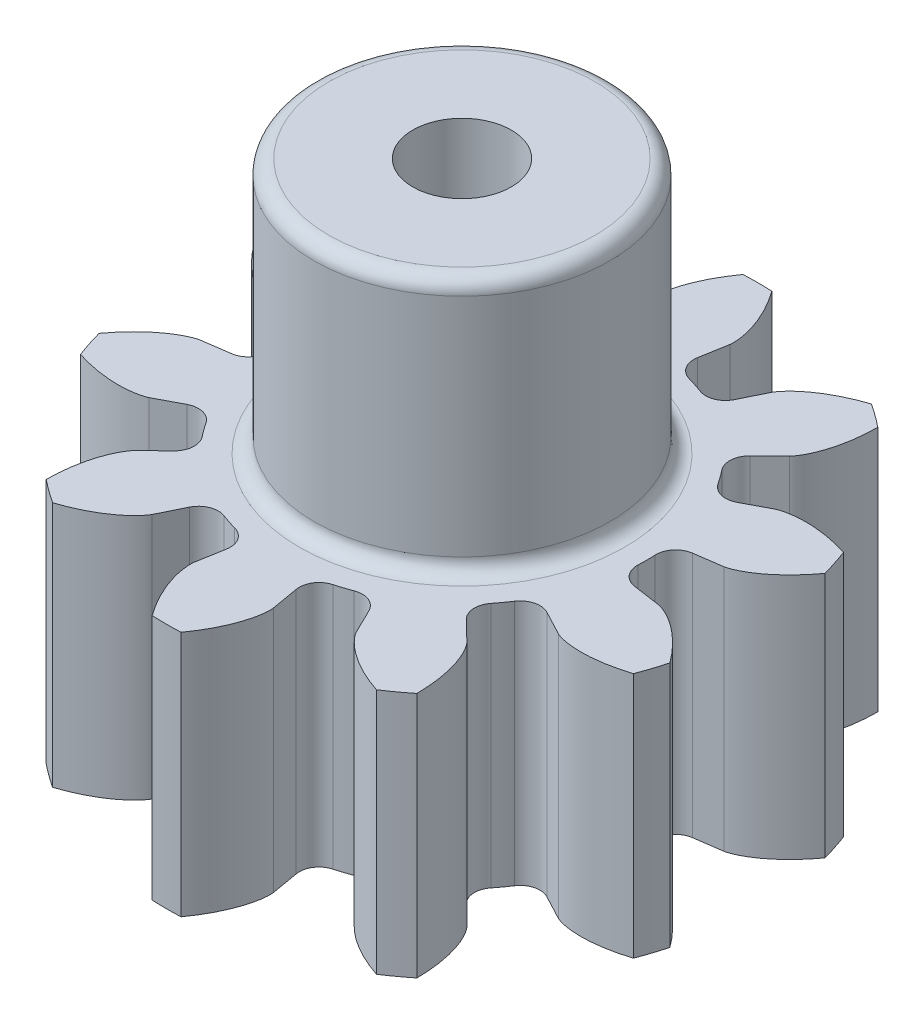
SolidWorks part; units mm, degrees
ref_plane "Front Plane" through (0, 0, 0) normal (0, 0, 1) x (1, 0, 0)
ref_plane "Top Plane" through (0, 0, 0) normal (0, 1, 0) x (1, 0, 0)
ref_plane "Right Plane" through (0, 0, 0) normal (1, 0, 0) x (0, 0, -1)
sketch "Sketch2" plane through (0, 0, 0) normal (0, 1, 0) x (1, 0, 0)
  circle A0 centre (0, 0) radius 15.24
  dimension "D1" = 30.48
extrude "Boss-Extrude1" add sketch "Sketch2" along normal blind 12.7
sketch "Sketch3" plane through (0, 0, 0) normal (0, -1, 0) x (-1, 0, 0)
  line L0 (0, 0) -> (11.8137, -1.691) construction
  line L1 (0, 0) -> (11.8137, 1.691) construction
  line L2 (11.8137, -1.691) -> (9.4289, -1.3497)
  line L3 (11.8137, 1.691) -> (9.4289, 1.3497)
  circle A0 centre (0, 0) radius 15.24
  circle A1 centre (0, 0) radius 12.7
  circle A2 centre (0, 0) radius 11.938
  circle A3 centre (0, 0) radius 9.525
  arc A4 (14.7073, 3.9942) -> (14.7073, -3.9942) centre (0, 0) cw
  arc A5 (9.4289, 1.3497) -> (9.4289, -1.3497) centre (0, 0) cw
  spline S0 degree 4 poles (11.8137, 1.691) (11.8192, 1.6919) (11.8345, 1.6947) (11.8634, 1.701) (11.9102, 1.7129) (11.9692, 1.7305) (12.0448, 1.7558) (12.1329, 1.789) (12.2286, 1.829) (12.3315, 1.8763) (12.433, 1.9267) (12.5329, 1.9801) (12.6314, 2.036) (12.7494, 2.1069) (12.8888, 2.1963) (13.0487, 2.3071) (13.2263, 2.4402) (13.4031, 2.5835) (13.5735, 2.7307) (13.7413, 2.8866) (13.9005, 3.0423) (14.0612, 3.2111) (14.2071, 3.3705) (14.3651, 3.5565) (14.4911, 3.7088) (14.6511, 3.9175) (14.7439, 4.0431) (14.8502, 4.1926) (14.8963, 4.2604) (14.9247, 4.3021) knots 0 0 0 0 0 0.005377 0.015084 0.028532 0.04661 0.064855 0.092111 0.119476 0.146842 0.174209 0.201575 0.228941 0.256307 0.307035 0.361767 0.4165 0.471232 0.525964 0.580697 0.635429 0.690161 0.744894 0.799626 0.854358 0.909091 0.954545 1 1 1 1 1 construction
  spline S1 degree 4 poles (11.8137, 1.691) (11.8192, 1.6919) (11.8345, 1.6947) (11.8634, 1.701) (11.9102, 1.7129) (11.9692, 1.7305) (12.0448, 1.7558) (12.1329, 1.789) (12.2286, 1.829) (12.3315, 1.8763) (12.433, 1.9267) (12.5329, 1.9801) (12.6314, 2.036) (12.7494, 2.1069) (12.8888, 2.1963) (13.0487, 2.3071) (13.2263, 2.4402) (13.4031, 2.5835) (13.5735, 2.7307) (13.7413, 2.8866) (13.9005, 3.0423) (14.0612, 3.2111) (14.2071, 3.3705) (14.3651, 3.5565) (14.4911, 3.7088) (14.6164, 3.8723) (14.6768, 3.9527) (14.7073, 3.9942) knots 0 0 0 0 0 0.005377 0.015084 0.028532 0.04661 0.064855 0.092111 0.119476 0.146842 0.174209 0.201575 0.228941 0.256307 0.307035 0.361767 0.4165 0.471232 0.525964 0.580697 0.635429 0.690161 0.744894 0.799626 0.854358 0.909091 0.909091 0.909091 0.909091 0.909091
  spline S2 degree 4 poles (11.8137, -1.691) (11.8192, -1.6919) (11.8345, -1.6947) (11.8634, -1.701) (11.9102, -1.7129) (11.9692, -1.7305) (12.0448, -1.7558) (12.1329, -1.789) (12.2286, -1.829) (12.3315, -1.8763) (12.433, -1.9267) (12.5329, -1.9801) (12.6314, -2.036) (12.7494, -2.1069) (12.8888, -2.1963) (13.0487, -2.3071) (13.2263, -2.4402) (13.4031, -2.5835) (13.5735, -2.7307) (13.7413, -2.8866) (13.9005, -3.0423) (14.0612, -3.2111) (14.2071, -3.3705) (14.3651, -3.5565) (14.4911, -3.7088) (14.6511, -3.9175) (14.7439, -4.0431) (14.8502, -4.1926) (14.8963, -4.2604) (14.9247, -4.3021) knots 0 0 0 0 0 0.005377 0.015084 0.028532 0.04661 0.064855 0.092111 0.119476 0.146842 0.174209 0.201575 0.228941 0.256307 0.307035 0.361767 0.4165 0.471232 0.525964 0.580697 0.635429 0.690161 0.744894 0.799626 0.854358 0.909091 0.954545 1 1 1 1 1 construction
  spline S3 degree 4 poles (11.8137, -1.691) (11.8192, -1.6919) (11.8345, -1.6947) (11.8634, -1.701) (11.9102, -1.7129) (11.9692, -1.7305) (12.0448, -1.7558) (12.1329, -1.789) (12.2286, -1.829) (12.3315, -1.8763) (12.433, -1.9267) (12.5329, -1.9801) (12.6314, -2.036) (12.7494, -2.1069) (12.8888, -2.1963) (13.0487, -2.3071) (13.2263, -2.4402) (13.4031, -2.5835) (13.5735, -2.7307) (13.7413, -2.8866) (13.9005, -3.0423) (14.0612, -3.2111) (14.2071, -3.3705) (14.3651, -3.5565) (14.4911, -3.7088) (14.6164, -3.8723) (14.6768, -3.9527) (14.7073, -3.9942) knots 0 0 0 0 0 0.005377 0.015084 0.028532 0.04661 0.064855 0.092111 0.119476 0.146842 0.174209 0.201575 0.228941 0.256307 0.307035 0.361767 0.4165 0.471232 0.525964 0.580697 0.635429 0.690161 0.744894 0.799626 0.854358 0.909091 0.909091 0.909091 0.909091 0.909091
  circle M5 centre (0, 0) radius 15.24
  dimension "D1" = 30.48
  dimension "D2" = 25.4
  dimension "D3" = 23.876
  dimension "D4" = 19.05
extrude "Cut-Extrude1" cut sketch "Sketch3" against normal through all contours A1 S3 S1 M5 | A2 S3 A1 S1 | L2 S3 A2 S1 L3 A3 region at (-10.7404, 0, 0) region at (-12.2842, 0, 0) region at (-14.0094, 0, 0)
fillet "Fillet1" radius 1.016 2 edges at (-9.4289, 6.35, -1.3497) (-9.4289, 6.35, 1.3497)
pattern_circular "CirPattern1" count 10 over 360 about axis through (0, 0, 0) along (0, 1, 0) of "Fillet1", "Cut-Extrude1"
sketch "Sketch4" plane through (0, 12.7, 0) normal (0, 1, 0) x (1, 0, 0)
  circle A1 centre (0, 0) radius 7.62
  dimension "D2" = 15.24
extrude "Boss-Extrude2" add sketch "Sketch4" along normal blind 13.16
sketch "Sketch5" plane through (0, 25.86, 0) normal (0, 1, 0) x (1, 0, 0)
  circle A0 centre (0, 0) radius 2.54
  dimension "D1" = 5.08
extrude "Cut-Extrude2" cut sketch "Sketch5" against normal through all
fillet "Fillet2" radius 0.762 2 edges at (0, 25.86, 7.62) (0, 12.7, 7.62)
equation "\"DiametralPitch\"= 10"
equation "\"NumTeeth\"= 10"
equation "\"PressureAngle\"= 20deg"
equation "\"Addendum\"= 1 / \"DiametralPitch\""
equation "\"Dedendum\"= 1.25 / \"DiametralPitch\""
equation "\"WorkingDepth\"= 2 / \"DiametralPitch\""
equation "\"WholeDepth\"= 2.25 / \"DiametralPitch\""
equation "\"Clearance\"= 0.3 / \"DiametralPitch\""
equation "\"ToothThickness\"= 1.5708 / \"DiametralPitch\""
equation "\"CircularPitch\"= pi / \"DiametralPitch\""
equation "\"PitchCircle\"= \"NumTeeth\" / \"DiametralPitch\""
equation "\"OutsideDiameter\"= ( \"NumTeeth\" + 2 ) / \"DiametralPitch\""
equation "\"Fillet\"= \"Clearance\" * cos ( \"PressureAngle\" ) * tan ( ( 90 + \"PressureAngle\" ) / 2 )"
equation "\"AddendumCircle\"= \"PitchCircle\" + ( 2 * \"Addendum\" )"
equation "\"DedendumCircle\"= \"PitchCircle\" - ( 2 * \"Dedendum\" )"
equation "\"BaseCircle\"= \"PitchCircle\" * cos ( \"PressureAngle\" )"
equation "\"PitchAngle\"= 360deg / \"NumTeeth\""
equation "\"Alpha\"= sqr ( \"PitchCircle\" ^ 2 - \"BaseCircle\" ^ 2 ) / \"BaseCircle\" * 180 / PI - \"PressureAngle\""
equation "\"Beta\"= ( \"PitchAngle\" / 4 - \"Alpha\" )"
equation "\"Phi\"= sqr ( ( \"AddendumCircle\" / 2 ) ^ 2 - ( \"BaseCircle\" / 2 ) ^ 2 ) / ( \"BaseCircle\" / 2 )"
